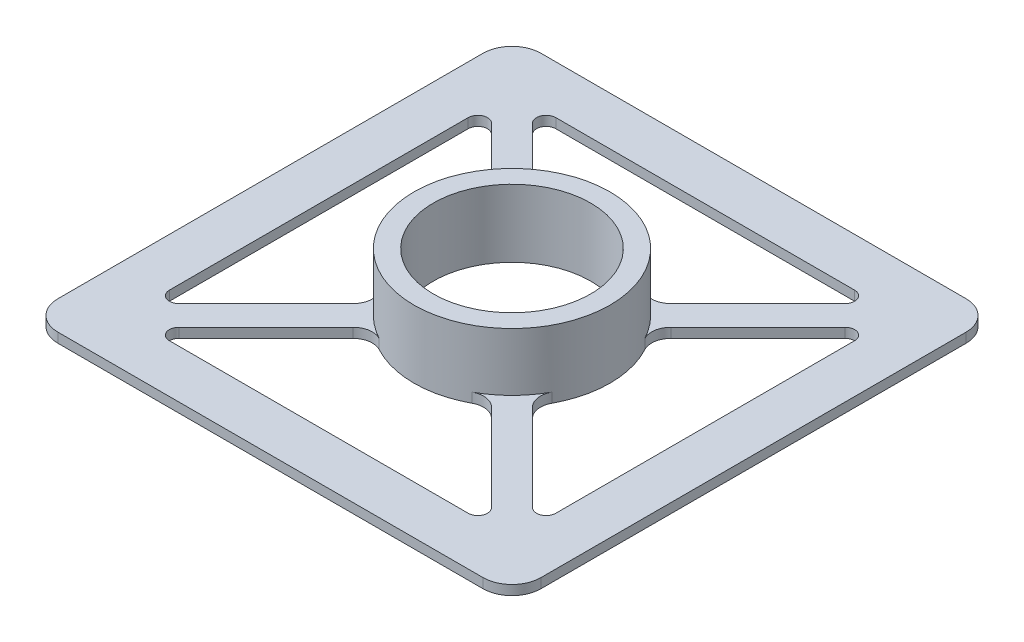
SolidWorks part; units mm, degrees
ref_plane "Front Plane" through (0, 0, 0) normal (0, 0, 1) x (1, 0, 0)
ref_plane "Top Plane" through (0, 0, 0) normal (0, 1, 0) x (1, 0, 0)
ref_plane "Right Plane" through (0, 0, 0) normal (1, 0, 0) x (0, 0, -1)
sketch "Sketch1" plane through (0, 0, 0) normal (0, 1, 0) x (1, 0, 0)
  line L0 (20, 17.8787) -> (20, -17.8787)
  line L1 (-25, -25) -> (25, -25)
  line L2 (-25, -25) -> (-25, 25)
  line L3 (-25, 25) -> (25, 25)
  line L4 (25, -25) -> (25, 25)
  line L5 (-25, -25) -> (25, 25) construction
  line L6 (-25, 25) -> (25, -25) construction
  line L7 (17.8787, -20) -> (-17.8787, -20)
  line L8 (-20, -17.8787) -> (-20, 17.8787)
  line L9 (-17.8787, 20) -> (17.8787, 20)
  line L10 (20, 17.8787) -> (8.159, 6.0377)
  line L11 (17.8787, 20) -> (6.0377, 8.159)
  line L12 (-17.8787, 20) -> (-6.0377, 8.159)
  line L13 (-20, 17.8787) -> (-8.159, 6.0377)
  line L14 (-20, -17.8787) -> (-8.159, -6.0377)
  line L15 (-17.8787, -20) -> (-6.0377, -8.159)
  line L16 (17.8787, -20) -> (6.0377, -8.159)
  line L17 (20, -17.8787) -> (8.159, -6.0377)
  circle A0 centre (0, 0) radius 8.15
  arc A1 (6.0377, 8.159) -> (-6.0377, 8.159) centre (0, 0) ccw
  circle A2 centre (0, 0) radius 10.15 construction
  arc A3 (-8.159, 6.0377) -> (-8.159, -6.0377) centre (0, 0) ccw
  arc A4 (-6.0377, -8.159) -> (6.0377, -8.159) centre (0, 0) ccw
  arc A5 (8.159, -6.0377) -> (8.159, 6.0377) centre (0, 0) ccw
  point P0 (0, 0)
  dimension "D1" = 16.3
  dimension "D3" = 50
  dimension "D4" = 50
  dimension "D5" = 5
  dimension "D6" = 1.5
  dimension "D7" = 1.5
  dimension "D8" = 1.5
  dimension "D9" = 1.5
  dimension "D10" = 1.5
  dimension "D11" = 1.5
  dimension "D12" = 1.5
  dimension "D13" = 1.5
  dimension "D2" = 2
base flange "Base-Flange1" sketch "Sketch1" thickness 1 reverse thickness direction no parameters "D1"=0.6
fillet "Fillet1" radius 3 4 edges at (25, -0.5, 25) (25, -0.5, -25) (-25, -0.5, -25) (-25, -0.5, 25)
fillet "Fillet2" radius 1 8 edges at (17.8787, -0.5, 20) (20, -0.5, 17.8787) (20, -0.5, -17.8787) (17.8787, -0.5, -20) (-17.8787, -0.5, 20) (-20, -0.5, 17.8787) (-17.8787, -0.5, -20) (-20, -0.5, -17.8787)
fillet "Fillet3" radius 2 8 edges at (6.0377, -0.5, 8.159) (-6.0377, -0.5, 8.159) (-6.0377, -0.5, -8.159) (8.159, -0.5, 6.0377) (8.159, -0.5, -6.0377) (6.0377, -0.5, -8.159) (-8.159, -0.5, -6.0377) (-8.159, -0.5, 6.0377)
sketch "Sketch2" plane through (0, 0, 0) normal (0, 1, 0) x (1, 0, 0)
  circle A0 centre (0, 0) radius 8.15
  circle A1 centre (0, 0) radius 10.15
  dimension "D2" = 16.3
  dimension "D1" = 2
extrude "Boss-Extrude1" add sketch "Sketch2" along normal blind 6
sketch "Bend-Lines1" plane through (0, 0, 0) normal (0, 1, 0) x (1, 0, 0)
sketch "Bounding-Box1" plane through (0, 0, 0) normal (0, 1, 0) x (1, 0, 0)
sheet metal parameters "Sheet-Metal(1)" thickness 1 parameters "D1"=0.6
flat pattern "Flat-Pattern(1)" [suppressed]
sketch "Bend-Lines2" plane through (0, 0, 0) normal (0, 1, 0) x (1, 0, 0)
sketch "Bounding-Box2" [suppressed] plane through (0, 0, 0) normal (0, 1, 0) x (1, 0, 0)
sheet metal parameters "Sheet-Metal(2)" thickness 1 parameters "D1"=0.6
flat pattern "Flat-Pattern(1)"
sketch "Bend-Lines2" plane through (0, 0, 0) normal (0, 1, 0) x (1, 0, 0)
sketch "Bounding-Box2" [suppressed] plane through (0, 0, 0) normal (0, 1, 0) x (1, 0, 0)
